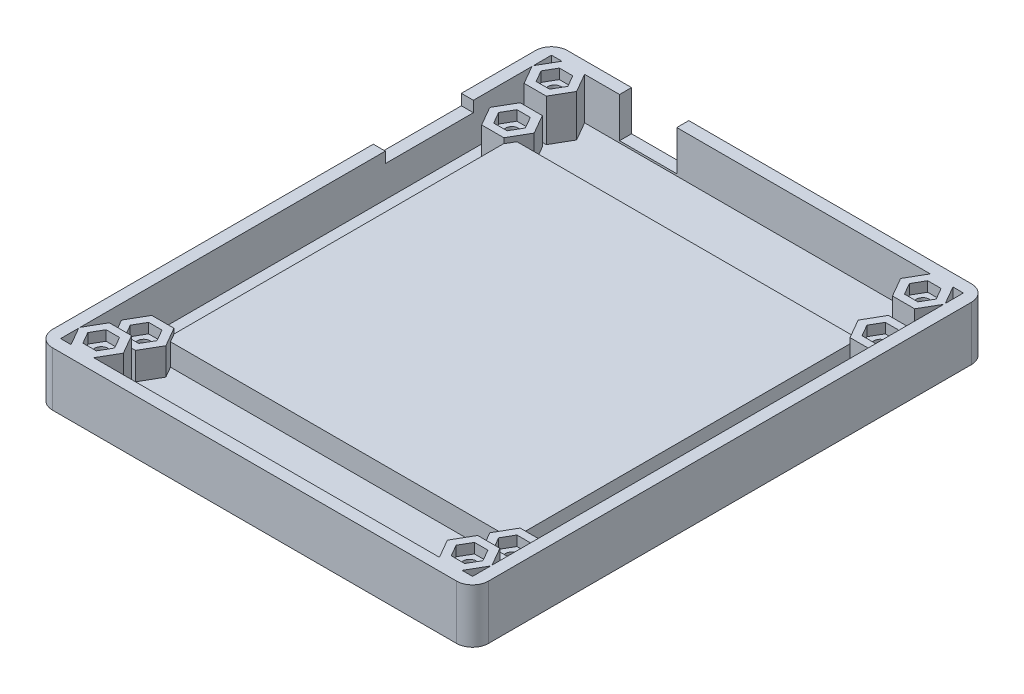
SolidWorks part; units mm, degrees
ref_plane "Přední rovina" through (0, 0, 0) normal (0, 0, 1) x (1, 0, 0)
ref_plane "Horní rovina" through (0, 0, 0) normal (0, 1, 0) x (1, 0, 0)
ref_plane "Pravá rovina" through (0, 0, 0) normal (1, 0, 0) x (0, 0, -1)
sketch "Skica1" plane through (0, 0, 0) normal (0, 1, 0) x (1, 0, 0)
  line L0 (0, 0) -> (-100, 100) construction
  line L1 (-50, 50) -> (50, 50) construction
  line L2 (-50, 50) -> (-50, -50) construction
  line L3 (-50, -50) -> (50, -50) construction
  line L4 (50, 50) -> (50, -50) construction
  line L5 (-50, 50) -> (50, -50) construction
  line L6 (-50, -50) -> (50, 50) construction
  line L7 (-47.6743, 43.1) -> (-44.3257, 43.1)
  line L8 (-44.3257, 43.1) -> (-42.6514, 46)
  line L9 (-42.6514, 46) -> (-44.3257, 48.9)
  line L10 (-44.3257, 48.9) -> (-47.6743, 48.9)
  line L11 (-47.6743, 48.9) -> (-49.3486, 46)
  line L12 (-49.3486, 46) -> (-47.6743, 43.1)
  line L13 (-48.7713, 41.2) -> (-43.2287, 41.2)
  line L14 (-43.2287, 41.2) -> (-40.4574, 46)
  line L15 (-40.4574, 46) -> (-43.2287, 50.8)
  line L16 (-43.2287, 50.8) -> (-48.7713, 50.8)
  line L17 (-48.7713, 50.8) -> (-51.5426, 46)
  line L18 (-51.5426, 46) -> (-48.7713, 41.2)
  line L19 (0, 81.3987) -> (0, -91.9033) construction
  line L20 (-42.6514, 56.6) -> (-44.3257, 59.5)
  line L21 (-44.3257, 59.5) -> (-47.6743, 59.5)
  line L22 (-47.6743, 59.5) -> (-49.3486, 56.6)
  line L23 (-49.3486, 56.6) -> (-47.6743, 53.7)
  line L24 (-47.6743, 53.7) -> (-44.3257, 53.7)
  line L25 (-44.3257, 53.7) -> (-42.6514, 56.6)
  line L26 (-48.7713, 51.8) -> (-43.2287, 51.8)
  line L27 (-43.2287, 51.8) -> (-40.4574, 56.6)
  line L28 (-40.4574, 56.6) -> (-43.2287, 61.4)
  line L29 (-43.2287, 61.4) -> (-48.7713, 61.4)
  line L30 (-48.7713, 61.4) -> (-51.5426, 56.6)
  line L31 (-51.5426, 56.6) -> (-48.7713, 51.8)
  line L36 (74.9355, -74.9355) -> (-74.9355, 74.9355) construction
  line L37 (74.9355, 74.9355) -> (-74.9355, -74.9355) construction
  line L38 (-54.4426, -64.3) -> (54.4426, -64.3)
  line L39 (-54.4426, -64.3) -> (-54.4426, 64.3)
  line L40 (-54.4426, 64.3) -> (54.4426, 64.3)
  line L41 (54.4426, -64.3) -> (54.4426, 64.3)
  line L42 (-54.4426, -64.3) -> (54.4426, 64.3) construction
  line L43 (-54.4426, 64.3) -> (54.4426, -64.3) construction
  line L44 (-106.951, 0) -> (125.2961, 0) construction
  line L45 (-46, 37.8836) -> (-46, 68.4593) construction
  line L47 (-51.4426, -61.3) -> (51.4426, -61.3)
  line L48 (-51.4426, -61.3) -> (-51.4426, 61.3)
  line L49 (-51.4426, 61.3) -> (51.4426, 61.3)
  line L50 (51.4426, -61.3) -> (51.4426, 61.3)
  line L51 (-51.4426, -61.3) -> (51.4426, 61.3) construction
  line L52 (-51.4426, 61.3) -> (51.4426, -61.3) construction
  circle A0 centre (-46, 46) radius 2.9 construction
  circle A1 centre (-46, 46) radius 4.8 construction
  circle A2 centre (-46, 56.6) radius 2.9 construction
  circle A3 centre (-46, 56.6) radius 4.8 construction
  circle A4 centre (-46, 46) radius 1.6
  circle A5 centre (-46, 56.6) radius 1.6
  point P0 (0, 0)
  point P7 (-41.8431, 43.6)
  dimension "D9" = 3
  dimension "D10" = 3
  dimension "D11" = 0.1
  dimension "D12" = 0.1
  dimension "D13" = 3.2
  dimension "D14" = 3.2
  dimension "D1" = 100
  dimension "D2" = 100
  dimension "D3" = 5.8
  dimension "D4" = 4
  dimension "D5" = 9.6
  dimension "D6" = 5.8
  dimension "D7" = 9.6
  dimension "D8" = 1
extrude "Přidat vysunutím25" add sketch "Skica1" against normal blind 3 contours L49 L48 L30 | L20 L21 L22 L23 L24 L25 | L7 L8 L9 L10 L11 L12 | L48 L47 L50 L49 | L13 L14 L15 L16 L17 L18 | L26 L27 L28 L29 L30 L31 region at (-50.5714, 0, -59.7911)
extrude "Přidat vysunutím26" add sketch "Skica1<21>" against normal blind 3 and the other way blind 10.5 contours L38 L41 L40 L39 L50 L47 L48 L18 L17 L31 L30 L49 L29 L28 | L18 L48 L17 | L31 L48 L30 | L30 L49 L28 L29 region at (-51.4759, 0, -46) region at (-51.4759, 0, -56.6) region at (-46, 0, -61.3498) region at (-52.7575, 0, 0)
sketch "Skica1<21>" plane through (0, 0, 0) normal (0, 1, 0) x (1, 0, 0) same geometry as "Skica1"
extrude "Přidat vysunutím28" add sketch "Skica1<23>" along normal blind 6.8 contours L48 L18 L13 L14 L15 L16 L17 L12 L11 L10 L9 L8 L7 | L18 L48 L17 region at (-49.9806, 0, -43.5863) region at (-51.4759, 0, -46)
sketch "Skica1<23>" plane through (0, 0, 0) normal (0, 1, 0) x (1, 0, 0) same geometry as "Skica1"
extrude "Přidat vysunutím29" add sketch "Skica1<24>" along normal blind 4.3 contours L11 L12 L7 L8 L9 L10 region at (-48.4347, 0, -44.5943)
sketch "Skica1<24>" plane through (0, 0, 0) normal (0, 1, 0) x (1, 0, 0) same geometry as "Skica1"
pattern_linear "LinPole3" count 2 spacing 92 along (1, 0, 0) count 2 spacing 92 along (0, 0, 1) of "Přidat vysunutím28", "Přidat vysunutím29"
extrude "Přidat vysunutím30" add sketch "Skica1<25>" along normal blind 10.5 contours L49 L30 L48 L31 L26 L27 L28 L25 L24 L23 L22 L21 L20 | L30 L49 L28 L29 | L31 L48 L30 region at (-51.2973, 0, -56.6) region at (-51.4759, 0, -56.6) region at (-46, 0, -61.3498)
sketch "Skica1<25>" plane through (0, 0, 0) normal (0, 1, 0) x (1, 0, 0) same geometry as "Skica1"
extrude "Přidat vysunutím31" add sketch "Skica1<26>" along normal blind 8 contours L24 L25 L20 L21 L22 L23 A5 region at (-43.5653, 0, -55.1943)
sketch "Skica1<26>" plane through (0, 0, 0) normal (0, 1, 0) x (1, 0, 0) same geometry as "Skica1"
pattern_linear "LinPole4" count 2 spacing 92 along (1, 0, 0) count 2 spacing 113.2 along (0, 0, 1) of "Přidat vysunutím31", "Přidat vysunutím30"
sketch "Skica8" plane through (0, 0, 0) normal (0, 1, 0) x (1, 0, 0)
  line L1 (-43.2691, -43.2691) -> (43.2691, -43.2691)
  line L2 (-43.2691, -43.2691) -> (-43.2691, 43.2691)
  line L3 (-43.2691, 43.2691) -> (43.2691, 43.2691)
  line L4 (43.2691, -43.2691) -> (43.2691, 43.2691)
  line L5 (-43.2691, -43.2691) -> (43.2691, 43.2691) construction
  line L6 (-43.2691, 43.2691) -> (43.2691, -43.2691) construction
  point P0 (0, 0)
  dimension "D1" = 86.5383
extrude "Přidat vysunutím32" add sketch "Skica8" along normal blind 5.5
fillet "Zaoblit4" radius 4 4 edges at (-54.4426, 3.75, 64.3) (54.4426, 3.75, 64.3) (54.4426, 3.75, -64.3) (-54.4426, 3.75, -64.3)
sketch "Skica9" plane through (-54.4426, 0, 0) normal (-1, 0, 0) x (0, 0, 1)
  line L0 (60.3, 10.5) -> (-60.3, 10.5) construction
  line L1 (-19.8, 7.8) -> (-41.8, 7.8)
  line L2 (-19.8, 7.8) -> (-19.8, 10.5)
  line L3 (-19.8, 10.5) -> (-41.8, 10.5)
  line L4 (-41.8, 7.8) -> (-41.8, 10.5)
  line L5 (-19.8, 7.8) -> (-41.8, 10.5) construction
  line L6 (-19.8, 10.5) -> (-41.8, 7.8) construction
  line L7 (-64.3, -3) -> (-64.3, 10.5) construction
  point P0 (-30.8, 9.15)
  dimension "D1" = 22
  dimension "D2" = 22.5
  dimension "D3" = 2.7
extrude "Odebrat vysunutím1" cut sketch "Skica9" against normal blind 10 contours L4 L3 L2 L1
sketch "Skica10" plane through (0, 0, -64.3) normal (0, 0, -1) x (-1, 0, 0)
  line L0 (50.4426, 10.5) -> (-50.4426, 10.5) construction
  line L1 (20.1426, 0.5) -> (34.4426, 0.5)
  line L2 (20.1426, 0.5) -> (20.1426, 10.5)
  line L3 (20.1426, 10.5) -> (34.4426, 10.5)
  line L4 (34.4426, 0.5) -> (34.4426, 10.5)
  line L5 (54.4426, 10.5) -> (54.4426, -3) construction
  dimension "D1" = 10
  dimension "D2" = 14.3
  dimension "D3" = 20
extrude "Odebrat vysunutím2" cut sketch "Skica10" against normal blind 5
